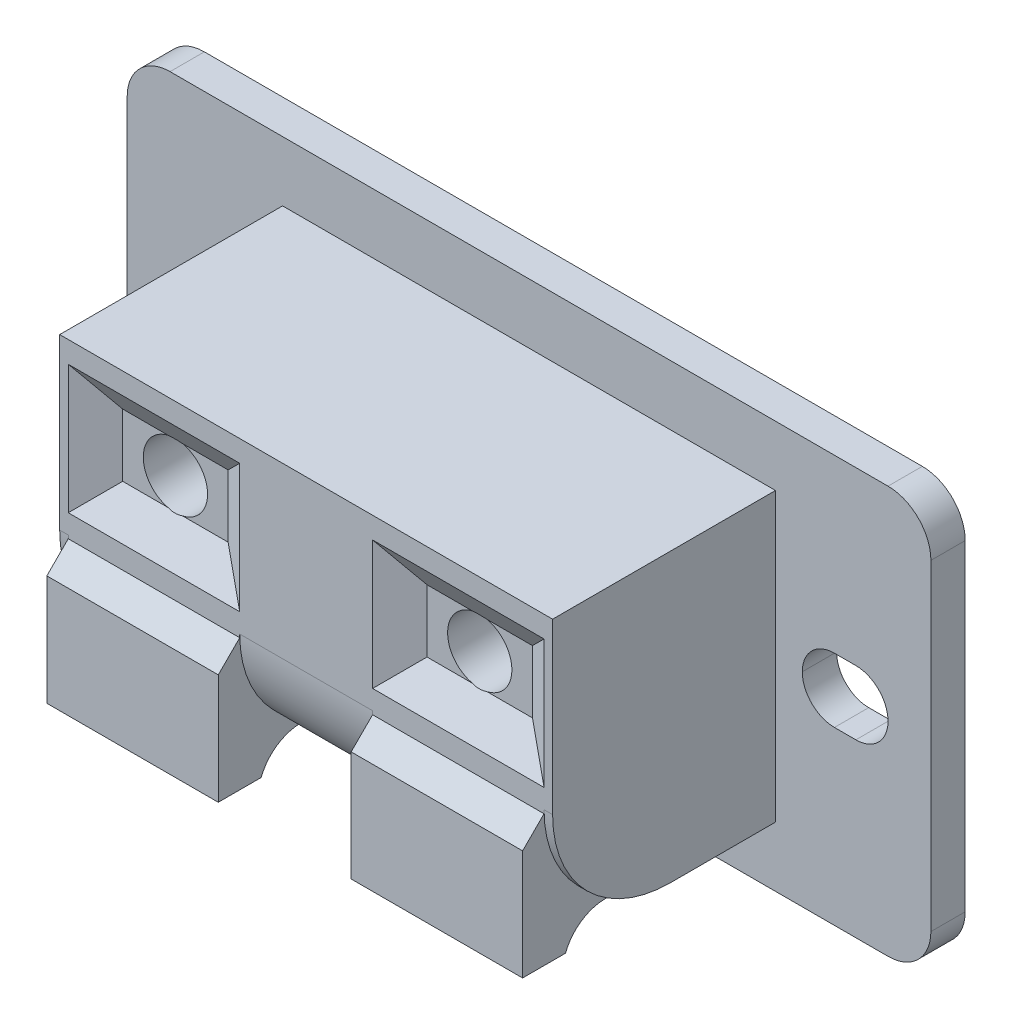
SolidWorks part; units mm, degrees
ref_plane "Спереди" through (0, 0, 0) normal (0, 0, 1) x (1, 0, 0)
ref_plane "Сверху" through (0, 0, 0) normal (0, 1, 0) x (1, 0, 0)
ref_plane "Справа" through (0, 0, 0) normal (1, 0, 0) x (0, 0, -1)
sketch "Эскиз2" plane through (0, 0, 0) normal (0, 0, 1) x (1, 0, 0)
  line L1 (-18.75, 9.5) -> (18.75, 9.5)
  line L2 (-18.75, 9.5) -> (-18.75, -9.5)
  line L3 (-18.75, -9.5) -> (18.75, -9.5)
  line L4 (18.75, 9.5) -> (18.75, -9.5)
  dimension "D1" = 19
  dimension "D2" = 37.5
  dimension "D3" = 9.5
  dimension "D4" = 18.75
extrude "Бобышка-Вытянуть1" add sketch "Эскиз2" along normal blind 1.6
sketch "Эскиз3" plane through (0, 0, 1.6) normal (0, 0, 1) x (1, 0, 0)
  line L1 (-11.5, 6.7) -> (11.5, 6.7)
  line L2 (-11.5, 6.7) -> (-11.5, -6.7)
  line L3 (-11.5, -6.7) -> (11.5, -6.7)
  line L4 (11.5, 6.7) -> (11.5, -6.7)
  dimension "D1" = 23
  dimension "D2" = 11.5
  dimension "D3" = 13.4
  dimension "D4" = 6.7
extrude "Бобышка-Вытянуть2" add sketch "Эскиз3" along normal blind 10.4
fillet "Скругление1" radius 2 4 edges at (18.75, 9.5, 0.8) (18.75, -9.5, 0.8) (-18.75, -9.5, 0.8) (-18.75, 9.5, 0.8)
sketch "Эскиз4" plane through (0, 0, 1.6) normal (0, 0, 1) x (1, 0, 0)
  line L0 (18.75, -7.5) -> (18.75, 7.5) construction
  line L1 (12.75, 1.5) -> (16.75, 1.5)
  line L2 (12.75, 1.5) -> (12.75, -1.5)
  line L3 (12.75, -1.5) -> (16.75, -1.5)
  line L4 (16.75, 1.5) -> (16.75, -1.5)
  line L5 (-16.75, 1.5) -> (-12.75, 1.5)
  line L6 (-16.75, 1.5) -> (-16.75, -1.5)
  line L7 (-16.75, -1.5) -> (-12.75, -1.5)
  line L8 (-12.75, 1.5) -> (-12.75, -1.5)
  line L9 (-18.75, 7.5) -> (-18.75, -7.5) construction
  dimension "D1" = 3
  dimension "D2" = 4
  dimension "D3" = 3
  dimension "D4" = 4
  dimension "D5" = 2
  dimension "D6" = 2
  dimension "D7" = 1.5
  dimension "D8" = 1.5
extrude "Вырез-Вытянуть1" cut sketch "Эскиз4" against normal blind 1.6
fillet "Скругление2" radius 1.5 8 edges at (-16.75, 1.5, 0.8) (-12.75, 1.5, 0.8) (16.75, 1.5, 0.8) (16.75, -1.5, 0.8) (-12.75, -1.5, 0.8) (-16.75, -1.5, 0.8) (12.75, -1.5, 0.8) (12.75, 1.5, 0.8)
sketch "Эскиз5" plane through (0, 0, 12) normal (0, 0, 1) x (1, 0, 0)
  line L0 (11.5, 6.7) -> (-11.5, 6.7) construction
  line L1 (11.5, -6.7) -> (11.5, 6.7) construction
  line L2 (-11.5, 6.7) -> (-11.5, -6.7) construction
  circle A0 centre (-7.1, 2.7) radius 1.5
  circle A1 centre (7.1, 2.7) radius 1.5
  dimension "D1" = 3
  dimension "D2" = 3
  dimension "D3" = 4
  dimension "D4" = 4
  dimension "D5" = 4.4
  dimension "D6" = 4.4
extrude "Вырез-Вытянуть2" cut sketch "Эскиз5" against normal blind 5
sketch "Эскиз6" plane through (0, 0, 12) normal (0, 0, 1) x (1, 0, 0)
  line L1 (-11.1, 5.7) -> (-3.1, 5.7)
  line L2 (-11.1, 5.7) -> (-11.1, -0.3)
  line L3 (-11.1, -0.3) -> (-3.1, -0.3)
  line L4 (-3.1, 5.7) -> (-3.1, -0.3)
  line L5 (3.1, 5.7) -> (11.1, 5.7)
  line L6 (3.1, 5.7) -> (3.1, -0.3)
  line L7 (3.1, -0.3) -> (11.1, -0.3)
  line L8 (11.1, 5.7) -> (11.1, -0.3)
  circle A0 centre (-7.1, 2.7) radius 1.5 construction
  circle A1 centre (-7.1, 2.7) radius 1.5 construction
  circle A2 centre (7.1, 2.7) radius 1.5 construction
  circle A3 centre (7.1, 2.7) radius 1.5 construction
  dimension "D6" = 4
  dimension "D8" = 3
  dimension "D1" = 6
  dimension "D2" = 8
  dimension "D3" = 8
  dimension "D4" = 6
  dimension "D5" = 3
  dimension "D7" = 4
extrude "Вырез-Вытянуть3" cut sketch "Эскиз6" against normal blind 1 draft 57
fillet "Скругление3" radius 5.5 1 edges at (0, -6.7, 12)
sketch "Эскиз7" plane through (0, 0, 12) normal (0, 0, 1) x (1, 0, 0)
  line L0 (-11.1, -0.3) -> (-3.1, -0.3) construction
  line L1 (-11.1, -0.5) -> (-3.1, -0.5)
  line L2 (-11.1, -0.5) -> (-11.1, -7.5)
  line L3 (-11.1, -7.5) -> (-3.1, -7.5)
  line L4 (-3.1, -0.5) -> (-3.1, -7.5)
  line L5 (3.1, -0.5) -> (11.1, -0.5)
  line L6 (3.1, -0.5) -> (3.1, -7.5)
  line L7 (3.1, -7.5) -> (11.1, -7.5)
  line L8 (11.1, -0.5) -> (11.1, -7.5)
  line L9 (3.1, -0.3) -> (11.1, -0.3) construction
  line L10 (11.1, -0.3) -> (11.1, 5.7) construction
  line L11 (3.1, 5.7) -> (3.1, -0.3) construction
  line L12 (-3.1, -0.3) -> (-3.1, 5.7) construction
  line L13 (-11.1, 5.7) -> (-11.1, -0.3) construction
  dimension "D1" = 0.2
  dimension "D2" = 0.2
  dimension "D3" = 7
  dimension "D4" = 7
extrude "Бобышка-Вытянуть3" add sketch "Эскиз7" against normal blind 1
sketch "Эскиз8" plane through (0, 0, 12) normal (0, 0, 1) x (1, 0, 0)
  line L0 (-3.1, -7.5) -> (-3.1, -1.2) construction
  line L1 (-11.1, -7.5) -> (-3.1, -7.5)
  line L2 (-11.1, -7.5) -> (-11.1, -4.35)
  line L3 (-11.1, -4.35) -> (-3.1, -4.35)
  line L4 (-3.1, -7.5) -> (-3.1, -4.35)
  line L6 (3.1, -7.5) -> (11.1, -7.5)
  line L7 (3.1, -7.5) -> (3.1, -4.3623)
  line L8 (3.1, -4.3623) -> (11.1, -4.3623)
  line L9 (11.1, -7.5) -> (11.1, -4.3623)
extrude "Бобышка-Вытянуть4" add sketch "Эскиз8" along normal blind 1
chamfer "Фаска1" distance 3 angle 45 2 edges at (-7.1, -4.35, 12) (7.1, -4.3623, 12)
fillet "Скругление4" radius 2 2 edges at (-7.1, -4.3623, 11) (7.1, -4.3623, 11)
sketch "Эскиз9" plane through (0, 0, 0) normal (0, 0, -1) x (-1, 0, 0)
  line L0 (-16.75, 9.5) -> (16.75, 9.5) construction
  line L1 (-7.75, 5.5) -> (-4.75, 5.5)
  line L2 (-7.75, 5.5) -> (-7.75, 5.3)
  line L3 (-7.75, 5.3) -> (-4.75, 5.3)
  line L4 (-4.75, 5.5) -> (-4.75, 5.3)
  line L5 (4.75, 5.5) -> (7.75, 5.5)
  line L6 (4.75, 5.5) -> (4.75, 5.3)
  line L7 (4.75, 5.3) -> (7.75, 5.3)
  line L8 (7.75, 5.5) -> (7.75, 5.3)
  line L9 (18.75, 7.5) -> (18.75, -7.5) construction
  line L10 (-18.75, -7.5) -> (-18.75, 7.5) construction
  dimension "D1" = 0.2
  dimension "D2" = 0.2
  dimension "D3" = 3
  dimension "D4" = 3
  dimension "D5" = 4
  dimension "D6" = 4
  dimension "D7" = 11
  dimension "D8" = 11
extrude "Бобышка-Вытянуть5" add sketch "Эскиз9" along normal blind 2
sketch "Эскиз10" plane through (0, 0, -2) normal (0, 0, -1) x (-1, 0, 0)
  line L0 (-4.75, 5.3) -> (-4.75, 5.5) construction
  line L1 (-7.75, 5.5) -> (-4.75, 5.5)
  line L2 (-7.75, 5.5) -> (-7.75, -1.5)
  line L3 (-7.75, -1.5) -> (-4.75, -1.5)
  line L4 (-4.75, 5.5) -> (-4.75, -1.5)
  line L5 (4.75, 5.5) -> (7.75, 5.5)
  line L6 (4.75, 5.5) -> (4.75, -1.5)
  line L7 (4.75, -1.5) -> (7.75, -1.5)
  line L8 (7.75, 5.5) -> (7.75, -1.5)
  line L9 (7.75, 5.3) -> (7.75, 5.5) construction
  dimension "D1" = 7
  dimension "D2" = 7
extrude "Бобышка-Вытянуть6" add sketch "Эскиз10" along normal blind 0.2
sketch "Эскиз11" plane through (0, 0, -2.2) normal (0, 0, -1) x (-1, 0, 0)
  line L0 (7.75, -1.5) -> (7.75, 5.5) construction
  line L1 (-7, 2.25) -> (-5.5, 2.25)
  line L2 (-7, 2.25) -> (-7, -0.75)
  line L3 (-7, -0.75) -> (-5.5, -0.75)
  line L4 (-5.5, 2.25) -> (-5.5, -0.75)
  line L5 (5.5, 2.25) -> (7, 2.25)
  line L6 (5.5, 2.25) -> (5.5, -0.75)
  line L7 (5.5, -0.75) -> (7, -0.75)
  line L8 (7, 2.25) -> (7, -0.75)
  line L9 (4.75, -1.5) -> (7.75, -1.5) construction
  line L10 (-4.75, -1.5) -> (-4.75, 5.5) construction
  line L11 (-7.75, -1.5) -> (-4.75, -1.5) construction
  dimension "D1" = 1.5
  dimension "D2" = 3
  dimension "D3" = 3
  dimension "D4" = 1.5
  dimension "D5" = 0.75
  dimension "D6" = 0.75
  dimension "D7" = 0.75
  dimension "D8" = 0.75
extrude "Вырез-Вытянуть4" cut sketch "Эскиз11" against normal blind 0.2
fillet "Скругление5" radius 0.75 12 edges at (-7, 2.25, -2.1) (-7, -0.75, -2.1) (5.5, -0.75, -2.1) (7, -0.75, -2.1) (-5.5, -0.75, -2.1) (-5.5, 2.25, -2.1) (4.75, -1.5, -2.1) (7, 2.25, -2.1) (7.75, -1.5, -2.1) (5.5, 2.25, -2.1) (-7.75, -1.5, -2.1) (-4.75, -1.5, -2.1)
